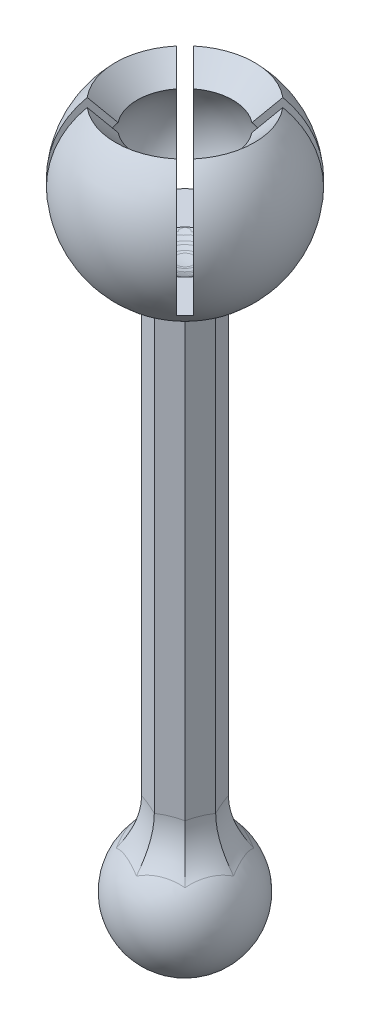
SolidWorks part; units mm, degrees
ref_plane "Front Plane" through (0, 0, 0) normal (0, 0, 1) x (1, 0, 0)
ref_plane "Top Plane" through (0, 0, 0) normal (0, 1, 0) x (1, 0, 0)
ref_plane "Right Plane" through (0, 0, 0) normal (1, 0, 0) x (0, 0, -1)
sketch "Sketch5" plane through (0, 0, 0) normal (0, 1, 0) x (1, 0, 0)
  line L0 (0, 2.5) -> (0, -2.5) construction
  line L1 (2.5, 0) -> (1.7678, 1.7678)
  line L2 (1.7678, 1.7678) -> (0, 2.5)
  line L3 (0, 2.5) -> (-1.7678, 1.7678)
  line L4 (-1.7678, 1.7678) -> (-2.5, 0)
  line L5 (-2.5, 0) -> (-1.7678, -1.7678)
  line L6 (-1.7678, -1.7678) -> (0, -2.5)
  line L7 (0, -2.5) -> (1.7678, -1.7678)
  line L8 (1.7678, -1.7678) -> (2.5, 0)
  circle A0 centre (0, 0) radius 2.3097 construction
  dimension "D1" = 5
extrude "Boss-Extrude2" add sketch "Sketch5" along normal mid plane 50
sketch "Sketch1" plane through (0, -25, 0) normal (0, 1, 0) x (1, 0, 0)
  line L0 (0, 5) -> (0, -5)
  arc A0 (0, 5) -> (0, -5) centre (0, 0) ccw
  dimension "D1" = 10
revolve "Revolve1" add sketch "Sketch1" angle 360 about L0
sketch "Sketch3" plane through (0, 0, 0) normal (0, 0, 1) x (1, 0, 0)
  line L1 (-5.6569, 30.6569) -> (-3.8891, 28.8891)
  line L2 (0, 19.5) -> (0, 17)
  line L3 (-1.7678, 25) -> (0, 25) construction
  line L4 (0, 25) -> (-5.5, 25) construction
  arc A0 (-3.8891, 28.8891) -> (0, 19.5) centre (0, 25) ccw
  arc A1 (-5.6569, 30.6569) -> (0, 17) centre (0, 25) ccw
  dimension "D1" = 5.5
  dimension "D2" = 2.5
  dimension "D3" = 45
  dimension "D4" = 1.6109
revolve "Revolve2" add sketch "Sketch3" angle 360 about L2
sketch "Sketch6" plane through (0, 25, 0) normal (0, 1, 0) x (1, 0, 0)
  line L0 (0.2747, -0.2747) -> (-0.2777, 0.2777) construction
  line L1 (0.0281, 0.0281) -> (-0.158, -0.158) construction
  line L2 (-0.7071, 0) -> (-6.0104, -5.3033)
  line L3 (5.3033, 6.0104) -> (6.0104, 5.3033)
  line L4 (5.3033, 6.0104) -> (0, 0.7071)
  line L5 (-6.0104, -5.3033) -> (-5.3033, -6.0104)
  line L6 (6.0104, 5.3033) -> (0.7071, 0)
  line L7 (-5.3033, 6.0104) -> (0, 0.7071)
  line L8 (-5.3033, 6.0104) -> (-6.0104, 5.3033)
  line L9 (-6.0104, 5.3033) -> (-0.7071, 0)
  line L10 (6.0104, -5.3033) -> (5.3033, -6.0104)
  line L11 (0.7071, 0) -> (6.0104, -5.3033)
  line L12 (0, -0.7071) -> (-5.3033, -6.0104)
  line L13 (0, -0.7071) -> (5.3033, -6.0104)
  line L14 (0, 0) -> (-8, 0) construction
  circle A0 centre (0, 0) radius 8 construction
  point P14 (-5.6569, 5.6569)
  point P15 (-5.6569, -5.6569)
  point P29 (5.6569, -5.6569)
  dimension "D1" = 1
sketch "Sketch4" plane through (0, 0, 0) normal (0, 0, 1) x (1, 0, 0)
  line L3 (0, 30.5) -> (0, 19.5)
  arc A0 (0, 30.5) -> (0, 19.5) centre (0, 25) ccw
  point P1 (0, 0)
  point P2 (0, 0)
  dimension "D1" = 11
revolve "Cut-Revolve1" cut sketch "Sketch4" angle 360 about L3
fillet "Fillet2" radius 5 8 edges at (-0.8839, -20.5654, 2.1339) (-2.1339, -20.5654, 0.8839) (-2.1339, -20.5654, -0.8839) (-0.8839, -20.5654, -2.1339) (0.8839, -20.5654, -2.1339) (2.1339, -20.5654, -0.8839) (2.1339, -20.5654, 0.8839) (0.8839, -20.5654, 2.1339)
extrude "Cut-Extrude3" cut sketch "Sketch6" along normal up to next and the other way up to vertex (4.899 mm away) other way up to point (1.7678, 20.101, -1.7678)
ref_plane "Plane1" through (1.25, 0, -1.25) normal (0.7071, 0, -0.7071) x (-0.7071, 0, -0.7071)
